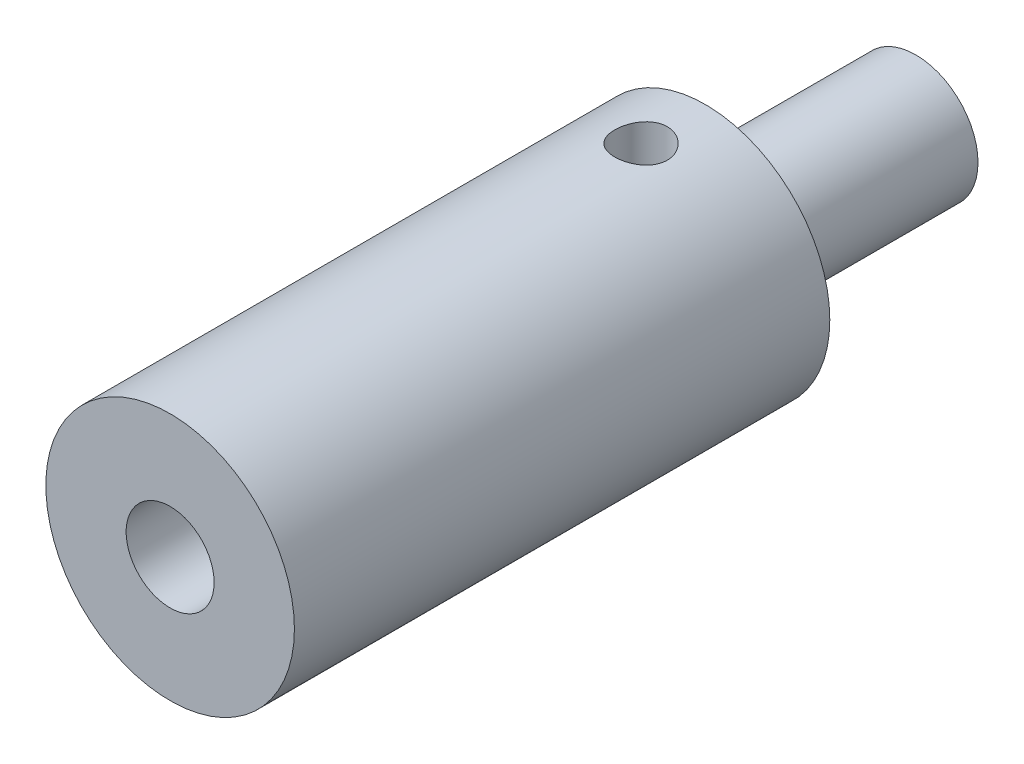
SolidWorks part; units mm, degrees
ref_plane "Alzado" through (0, 0, 0) normal (0, 0, 1) x (1, 0, 0)
ref_plane "Planta" through (0, 0, 0) normal (0, 1, 0) x (1, 0, 0)
ref_plane "Vista lateral" through (0, 0, 0) normal (1, 0, 0) x (0, 0, -1)
sketch "Croquis1" plane through (0, 0, 0) normal (0, 0, 1) x (1, 0, 0)
  circle A0 centre (0, 0) radius 13
  circle A1 centre (0, 0) radius 4.6
  dimension "D1" = 9.2
  dimension "D2" = 26
extrude "Saliente-Extruir1" add sketch "Croquis1" along normal blind 40
extrude "Saliente-Extruir2" add sketch "Croquis1<2>" against normal blind 16 contours A1 | A0 A1 region at (-12.6323, 0, 0) region at (0, 0, 0)
sketch "Croquis1<2>" plane through (0, 0, 0) normal (0, 0, 1) x (1, 0, 0) same geometry as "Croquis1"
sketch "Croquis2" plane through (0, 0, -16) normal (0, 0, -1) x (-1, 0, 0)
  circle A0 centre (0, 0) radius 6.5
  dimension "D1" = 13
extrude "Saliente-Extruir3" add sketch "Croquis2" along normal blind 22
fillet "Redondeo1" radius 0.5 1 edges at (-6.5, 0, -16)
fillet "Redondeo2" radius 0.5 1 edges at (4.6, 0, 0)
sketch "Croquis3" plane through (0, 0, 0) normal (0, 1, 0) x (1, 0, 0)
  line L1 (-24.5355, 12) -> (24.9531, 12) construction
  line L2 (13, 16) -> (-13, 16) construction
  circle A0 centre (0, 9.25) radius 2.75
  point P2 (24.9531, 8.3966)
  dimension "D1" = 5.5
  dimension "D2" = 4
extrude "Cortar-Extruir1" cut sketch "Croquis3" against normal through all both and the other way through all
